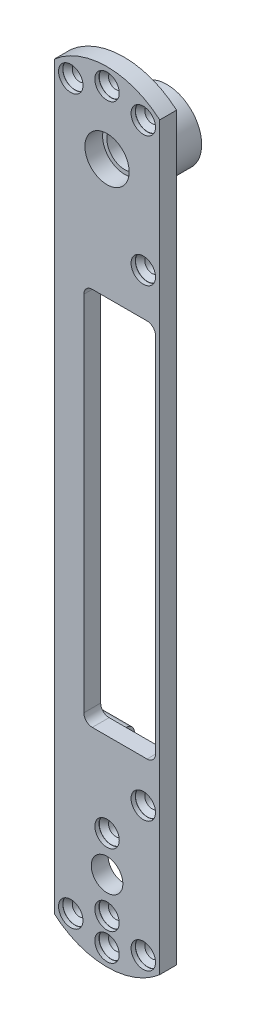
SolidWorks part; units mm, degrees
ref_plane "Front Plane" through (0, 0, 0) normal (0, 0, 1) x (1, 0, 0)
ref_plane "Top Plane" through (0, 0, 0) normal (0, 1, 0) x (1, 0, 0)
ref_plane "Right Plane" through (0, 0, 0) normal (1, 0, 0) x (0, 0, -1)
sketch "Sketch1" plane through (0, 0, 0) normal (0, 0, 1) x (1, 0, 0)
  line L0 (18.375, 147) -> (18.375, 0)
  line L1 (43.375, 147) -> (43.375, 0)
  circle A0 centre (30.875, 8.5) radius 1.75
  circle A1 centre (30.875, 0) radius 12.5 construction
  circle A2 centre (30.875, 0) radius 12.5
  circle A3 centre (30.875, -8.5) radius 1.75
  circle A4 centre (30.875, 0) radius 3.75
  circle A5 centre (30.875, -8.5) radius 1.25 construction
  circle A6 centre (30.875, 147) radius 12.5
  circle A7 centre (30.875, 147) radius 5.25
  circle A8 centre (30.875, 147) radius 5 construction
  circle A11 centre (30.875, 8.5) radius 1.25 construction
  circle A12 centre (30.875, 147) radius 5 construction
  point P20 (0, 0)
  point P21 (0, 0)
  point P25 (0, 0)
  point P26 (0, 0)
  dimension "D2" = 3.5
  dimension "D3" = 7.5
  dimension "D1" = 0.25
extrude "Boss-Extrude1" add sketch "Sketch1" along normal blind 4 contours A6 | A6 L0 A2 L1 | A2 A4 A3 A0 region at (30.875, 73.5, 0) region at (30.875, 159.1464, 0) region at (30.875, 12.1464, 0)
sketch "Sketch2" plane through (0, 0, 0) normal (0, 0, 1) x (1, 0, 0)
  circle A0 centre (30.875, 147) radius 5.25
  circle A1 centre (30.875, 147) radius 5.25 construction
  circle A2 centre (30.875, 147) radius 8.25
  dimension "D1" = 3
extrude "Boss-Extrude2" add sketch "Sketch2" against normal blind 0.2
sketch "Sketch3" plane through (0, 0, -0.2) normal (0, 0, -1) x (-1, 0, 0)
  circle A0 centre (-30.875, 147) radius 8.25 construction
  circle A1 centre (-30.875, 147) radius 8.25
  circle A2 centre (-30.875, 147) radius 4.25
  circle A3 centre (-30.875, 147) radius 5.25 construction
  dimension "D1" = 1
extrude "Boss-Extrude3" add sketch "Sketch3" along normal blind 5.8
sketch "Sketch4" plane through (0, 0, -6) normal (0, 0, -1) x (-1, 0, 0)
  circle A0 centre (-30.875, 147) radius 8.25 construction
  circle A1 centre (-30.875, 147) radius 8.25
  circle A2 centre (-30.875, 147) radius 5.25
  circle A3 centre (-30.875, 147) radius 5.25 construction
extrude "Boss-Extrude4" add sketch "Sketch4" along normal blind 4.2
sketch "Sketch9" plane through (0, 0, 0) normal (0, 0, -1) x (-1, 0, 0)
  line L0 (-43.375, 161.3091) -> (-43.375, -14.3091)
  line L1 (-43.375, 147) -> (-43.375, 0) construction
  line L2 (-18.375, 161.3091) -> (-18.375, -14.3091)
  line L3 (-18.375, 147) -> (-18.375, 0) construction
  circle A0 centre (-30.875, 147) radius 19
  circle A1 centre (-30.875, 0) radius 19
  arc A2 (-18.375, 147) -> (-43.375, 147) centre (-30.875, 147) ccw construction
  arc M15 (-18.375, 147) -> (-43.375, 147) centre (-30.875, 147) ccw
  arc M17 (-43.375, 0) -> (-18.375, 0) centre (-30.875, 0) ccw
  dimension "D1" = 6.5
extrude "Boss-Extrude5" add sketch "Sketch9" against normal up to surface (4 mm away) contours L2 A0 L0 M15 | L0 A1 L2 M17 region at (30.875, 160.2864, 0) region at (30.875, -13.2864, 0) up to face at (36.125, 147, 4)
sketch "Sketch10" plane through (0, 0, 4) normal (0, 0, 1) x (1, 0, 0)
  line L0 (30.875, 166) -> (30.875, -19) construction
  line L1 (30.875, 147) -> (19.977, 162.5639) construction
  line L2 (39.4786, 159.2873) -> (39.4786, -12.2873) construction
  line L3 (18.375, 73.5) -> (43.375, 73.5) construction
  line L4 (18.375, 161.3091) -> (18.375, -14.3091) construction
  line L5 (43.375, 161.3091) -> (43.375, -14.3091) construction
  circle A0 centre (30.875, 147) radius 15
  arc A1 (43.375, 161.3091) -> (18.375, 161.3091) centre (30.875, 147) ccw construction
  arc A2 (18.375, -14.3091) -> (43.375, -14.3091) centre (30.875, 0) ccw construction
  circle A3 centre (30.875, 162) radius 1.75
  circle A4 centre (22.2714, 159.2873) radius 1.75
  circle A5 centre (39.4786, 159.2873) radius 1.75
  circle A6 centre (39.4786, -12.2873) radius 1.75
  circle A7 centre (30.875, -15) radius 1.75
  circle A8 centre (22.2714, -12.2873) radius 1.75
  circle A9 centre (39.4786, 128.5) radius 1.75
  circle A10 centre (39.4786, 18.5) radius 1.75
  dimension "D1" = 4
  dimension "D2" = 3.5
  dimension "D3" = 35
  dimension "D4" = 110
extrude "Cut-Extrude4" cut sketch "Sketch10" against normal up to next contours A0 A4 | A0 A4 | A0 A3 | A0 A3 | A5 A0 | A5 A0 | A8 | A7 | A6 | A9 | A10 region at (39.0423, 158.6641, 4) region at (39.8939, 159.8804, 4) region at (21.8561, 159.8804, 4) region at (22.7077, 158.6641, 4) region at (30.875, 161.2392, 4) region at (30.875, 162.724, 4) region at (39.4786, -12.2873, 4) region at (30.875, -15, 4) region at (22.2714, -12.2873, 4) region at (39.4786, 128.5, 4) region at (39.4786, 18.5, 4)
sketch "Sketch8" plane through (0, 0, 4) normal (0, 0, 1) x (1, 0, 0)
  circle A0 centre (30.875, 8.5) radius 2.9
  circle A1 centre (30.875, -8.5) radius 2.9
  circle A2 centre (22.2714, -12.2873) radius 2.9
  circle A3 centre (30.875, -15) radius 2.9
  circle A4 centre (39.4786, -12.2873) radius 2.9
  circle A5 centre (22.2714, 159.2873) radius 2.9
  circle A6 centre (30.875, 162) radius 2.9
  circle A7 centre (39.4786, 159.2873) radius 2.9
  circle A8 centre (39.4786, 159.2873) radius 1.75 construction
  circle A9 centre (39.4786, -12.2873) radius 1.75 construction
  circle A10 centre (22.2714, -12.2873) radius 1.75 construction
  circle A11 centre (30.875, -15) radius 1.75 construction
  circle A12 centre (39.4786, 128.5) radius 2.9
  circle A13 centre (39.4786, 18.5) radius 2.9
  circle M10 centre (30.875, -8.5) radius 1.75
  circle M11 centre (30.875, 8.5) radius 1.75
  circle M59 centre (39.4786, 18.5) radius 1.75
  circle M60 centre (39.4786, 128.5) radius 1.75
  dimension "D1" = 5.8
extrude "Cut-Extrude3" cut sketch "Sketch8" against normal blind 1 contours A5 | A6 | A7 | A2 | A3 | A4 | A0 M11 | A1 M10 | A12 M60 | A13 M59 region at (28.057, 8.5, 4) region at (28.057, -8.5, 4) region at (22.2714, -12.2873, 4) region at (30.875, -15, 4) region at (39.4786, -12.2873, 4) region at (22.2714, 159.2873, 4) region at (30.875, 162, 4) region at (39.4786, 159.2873, 4) region at (36.6607, 128.5, 4) region at (36.6607, 18.5, 4)
chamfer "Chamfer1" distance 1.1 angle 45 10 edges at (41.2286, -12.2873, 3) (32.625, -15, 3) (24.0214, -12.2873, 3) (41.2286, 159.2873, 3) (32.625, 162, 3) (24.0214, 159.2873, 3) (32.625, -8.5, 3) (32.625, 8.5, 3) (41.2286, 18.5, 3) (41.2286, 128.5, 3)
sketch "Sketch11" plane through (0, 0, 4) normal (0, 0, 1) x (1, 0, 0)
  line L0 (43.375, 161.3091) -> (43.375, -14.3091) construction
  line L1 (25.375, 28.5) -> (42.375, 28.5)
  line L2 (25.375, 28.5) -> (25.375, 118.5)
  line L3 (25.375, 118.5) -> (42.375, 118.5)
  line L4 (42.375, 28.5) -> (42.375, 118.5)
  line L5 (18.375, 73.5) -> (43.375, 73.5) construction
  line L6 (18.375, 161.3091) -> (18.375, -14.3091) construction
  line L7 (25.375, 73.5) -> (42.375, 73.5) construction
  dimension "D1" = 1
  dimension "D2" = 90
  dimension "D3" = 17
extrude "Cut-Extrude5" cut sketch "Sketch11" against normal up to next
sketch "Sketch12" plane through (0, 0, 0) normal (0, 0, -1) x (-1, 0, 0)
  line L0 (-18.375, 161.3091) -> (-18.375, -14.3091) construction
  line L1 (-18.375, 132.5) -> (-25.375, 132.5)
  line L2 (-18.375, 132.5) -> (-18.375, 124.5)
  line L3 (-18.375, 124.5) -> (-25.375, 124.5)
  line L4 (-25.375, 132.5) -> (-25.375, 124.5)
  line L5 (-25.375, 128.5) -> (-18.375, 128.5) construction
  line L6 (-37.7286, 128.5) -> (-41.2286, 128.5) construction
  circle A0 centre (-39.4786, 128.5) radius 1.75 construction
  dimension "D1" = 8
  dimension "D2" = 7
extrude "Boss-Extrude6" add sketch "Sketch12" along normal blind 8
sketch "Sketch13" plane through (18.375, 0, 0) normal (-1, 0, 0) x (0, 0, 1)
  line L0 (0, 132.5) -> (-8, 124.5) construction
  line L1 (0, 124.5) -> (-8, 132.5) construction
  line L2 (-5.7321, 131.5) -> (-8, 131.5)
  line L3 (-7.4641, 128.5) -> (-5.7321, 125.5)
  line L4 (-5.7321, 125.5) -> (-2.2679, 125.5)
  line L5 (-2.2679, 125.5) -> (-0.5359, 128.5)
  line L6 (-0.5359, 128.5) -> (-2.2679, 131.5)
  line L7 (-2.2679, 131.5) -> (-5.7321, 131.5)
  line L8 (-5.7321, 131.5) -> (-7.4641, 128.5)
  line L9 (-8, 124.5) -> (-8, 132.5) construction
  line L10 (-5.7321, 125.5) -> (-8, 125.5)
  circle A0 centre (-4, 128.5) radius 3 construction
  line M5 (-8, 132.5) -> (-8, 124.5)
  dimension "D1" = 6
extrude "Cut-Extrude6" cut sketch "Sketch13" against normal blind 2.5 from offset 2.5 contours L10 L3 L8 L2 M5 | L7 L8 L3 L4 L5 L6 region at (18.375, 130.0321, -6.6536) region at (18.375, 128.5, -4) offset against normal yes
sketch "Sketch14" plane through (18.375, 0, 0) normal (-1, 0, 0) x (0, 0, 1)
  line L0 (0, 132.5) -> (-8, 124.5) construction
  line L1 (-8, 132.5) -> (0, 124.5) construction
  circle A0 centre (-4, 128.5) radius 1.75
  dimension "D1" = 3.5
extrude "Cut-Extrude7" cut sketch "Sketch14" against normal up to surface (7 mm away) up to face at (25.375, 128.5, -4)
fillet "Fillet1" radius 2 4 edges at (21.875, 132.5, 0) (21.875, 132.5, -8) (21.875, 124.5, -8) (21.875, 124.5, 0)
sketch "Sketch15" plane through (0, 0, 0) normal (0, 0, -1) x (-1, 0, 0)
  line L0 (-30.875, 166) -> (-30.875, -19) construction
  line L1 (-43.375, 73.5) -> (-18.375, 73.5) construction
  line L2 (-43.375, 161.3091) -> (-43.375, -14.3091) construction
  line L3 (-18.375, 122.5) -> (-18.375, -14.3091) construction
  arc A0 (-18.375, 161.3091) -> (-43.375, 161.3091) centre (-30.875, 147) ccw construction
  arc A1 (-43.375, -14.3091) -> (-18.375, -14.3091) centre (-30.875, 0) ccw construction
  point P16 (-30.875, 73.5)
ref_plane "Plane1" through (0, 73.5, 0) normal (0, 1, 0) x (1, 0, 0)
mirror "Mirror1" about plane through (0, 73.5, 0) normal (0, 1, 0) of "Fillet1", "Cut-Extrude7", "Cut-Extrude6", "Boss-Extrude6"
fillet "Fillet2" radius 2 5 edges at (42.375, 28.5, 2) (25.375, 28.5, 2) (25.375, 118.5, 2) (42.375, 118.5, 2) (39.125, 147, 0)
